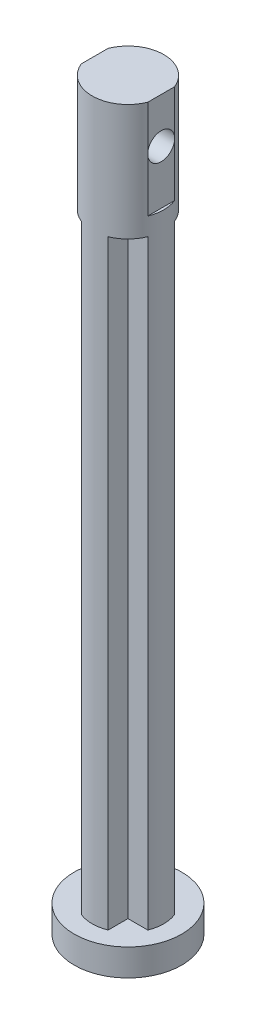
SolidWorks part; units mm, degrees
ref_plane "Front Plane" through (0, 0, 0) normal (0, 0, 1) x (1, 0, 0)
ref_plane "Top Plane" through (0, 0, 0) normal (0, 1, 0) x (1, 0, 0)
ref_plane "Right Plane" through (0, 0, 0) normal (1, 0, 0) x (0, 0, -1)
sketch "Sketch1" plane through (0, 0, 0) normal (0, 1, 0) x (1, 0, 0)
  line L0 (1.5, 3.7081) -> (1.5, 1.5)
  line L1 (-1.5, 3.7081) -> (-1.5, 1.5)
  line L2 (0, 0.9951) -> (0, -0.8681) construction
  line L3 (3.7081, -1.5) -> (1.5, -1.5)
  line L4 (3.7081, 1.5) -> (1.5, 1.5)
  line L5 (-1.5, -3.7081) -> (-1.5, -1.5)
  line L6 (1.5, -3.7081) -> (1.5, -1.5)
  line L7 (-3.7081, 1.5) -> (-1.5, 1.5)
  line L8 (-3.7081, -1.5) -> (-1.5, -1.5)
  circle A0 centre (0, 0) radius 6
  circle A1 centre (0, 0) radius 4
  point P25 (0, 0)
  dimension "D1" = 12
  dimension "D2" = 8
  dimension "D3" = 3
  dimension "D4" = 1.5
  dimension "D5" = 4
extrude "Boss-Extrude1" add sketch "Sketch1" against normal blind 67 contours L3 A1 L4 L0 L1 L7 L8 L5 L6 region at (0, 0, 0)
extrude "Boss-Extrude2" add sketch "Sketch1<3>" along normal blind 13 contours A1
sketch "Sketch1<3>" plane through (0, 0, 0) normal (0, 1, 0) x (1, 0, 0) same geometry as "Sketch1"
extrude "Boss-Extrude3" add sketch "Sketch1<4>" against normal blind 3 from offset 67 contours A0 A1 | L6 A1 L3 | L8 A1 L5 | L4 A1 L0 | L1 A1 L7 | L3 A1 L4 L0 L1 L7 L8 L5 L6 region at (2.3343, 0, -2.3343) region at (0, 0, 0) region at (-2.3343, 0, -2.3343) region at (2.3343, 0, 2.3343) region at (-2.3343, 0, 2.3343) region at (-5.8303, 0, 0) offset against normal yes
sketch "Sketch1<4>" plane through (0, 0, 0) normal (0, 1, 0) x (1, 0, 0) same geometry as "Sketch1"
sketch "Sketch2" plane through (0, 13, 0) normal (0, 1, 0) x (1, 0, 0)
  line L0 (3.7081, 1.5) -> (3.7081, -1.5)
  line L2 (0, 0.6885) -> (0, -0.3692) construction
  circle A0 centre (0, 0) radius 4 construction
  arc A1 (3.7081, -1.5) -> (3.7081, 1.5) centre (0, 0) ccw
  point P5 (0, 0)
  point P9 (-0.2919, 3.9893)
  point P10 (3.7081, 1.5)
  point P11 (0, 0)
  point P12 (2, 3.4641)
  point P13 (2, 0.4641)
  point P14 (2, 0.4641)
  point P15 (0, 0)
  point P16 (3.6062, 1.7307)
  point P17 (3.6895, -1.4548)
  point P18 (0, 0)
  point P19 (0, 0)
  dimension "D1" = 3
extrude "Cut-Extrude1" cut sketch "Sketch2" against normal blind 11
sketch "Sketch3" plane through (3.7081, 0, 0) normal (1, 0, 0) x (0, 0, -1)
  line L0 (1.5, 2) -> (1.5, 13) construction
  line L1 (-1.5, 2) -> (-1.5, 13) construction
  line L2 (1.5, 13) -> (-1.5, 13) construction
  circle A0 centre (0, 8) radius 1.5
  dimension "D1" = 5
extrude "Cut-Extrude2" cut sketch "Sketch3" against normal blind 4
mirror "Mirror1" about plane through (0, 0, 0) normal (1, 0, 0) of "Cut-Extrude2", "Cut-Extrude1"
